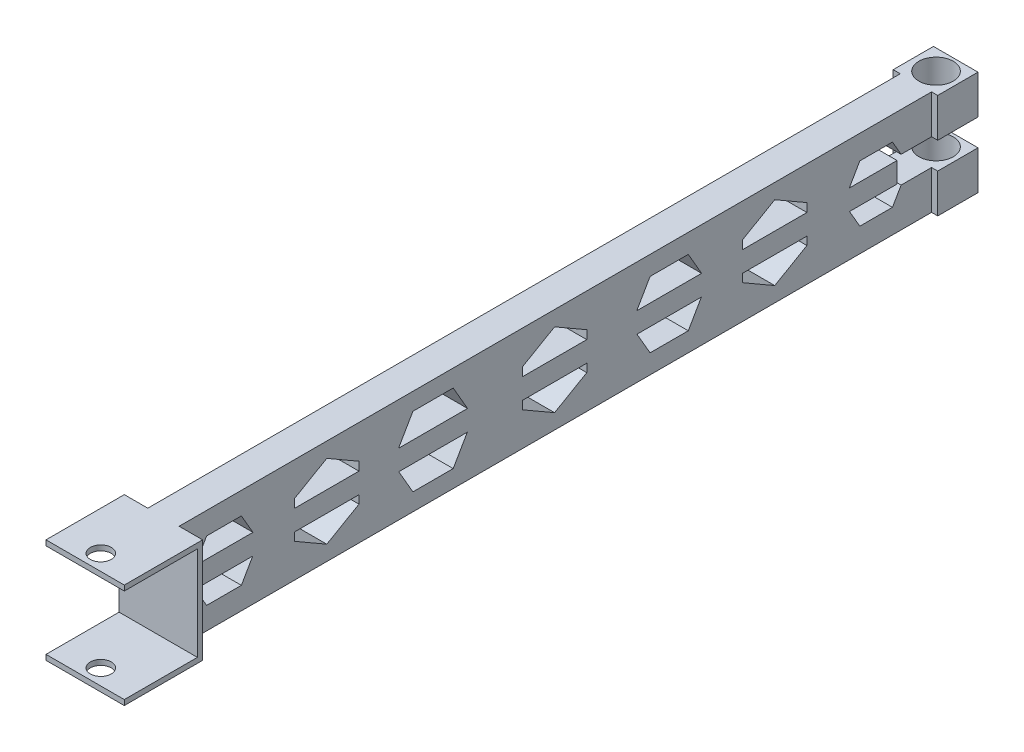
SolidWorks part; units mm, degrees
ref_plane "前视基准面" through (0, 0, 0) normal (0, 0, 1) x (1, 0, 0)
ref_plane "上视基准面" through (0, 0, 0) normal (0, 1, 0) x (1, 0, 0)
ref_plane "右视基准面" through (0, 0, 0) normal (1, 0, 0) x (0, 0, -1)
sketch "草图1" plane through (0, 0, 0) normal (0, 0, 1) x (1, 0, 0)
  line L1 (-3, -10) -> (3, -10)
  line L2 (-3, -10) -> (-3, 10)
  line L3 (-3, 10) -> (3, 10)
  line L4 (3, -10) -> (3, 10)
  line L5 (-3, -10) -> (3, 10) construction
  line L6 (-3, 10) -> (3, -10) construction
  point P0 (0, 0)
extrude "凸台-拉伸1" add sketch "草图1" along normal blind 165
sketch "草图2" plane through (3, 0, 0) normal (1, 0, 0) x (0, 0, -1)
  line L0 (0, 0) -> (-5, 0)
hole_wizard "G1/16 螺纹孔1" positions "草图3" profile "草图4" tap size "G1/16" standard "GB"
sketch "草图3" plane through (3, 0, 0) normal (1, 0, 0) x (0, 0, -1)
  point P0 (-5, 0)
sketch "草图4" plane through (3, 0, 5) normal (0, 1, 0) x (0, 0, -1)
  line L0 (0, 0) -> (0, 51.9828)
  line L1 (0, 51.9828) -> (3.3, 50)
  line L2 (3.3, 50) -> (3.3, 0.5865)
  line L3 (3.3, 0.5865) -> (3.8865, 0)
  line L5 (3.8865, 0) -> (0, 0)
  line L6 (-3.3, 0.5865) -> (-3.8865, 0) construction
  line L10 (0, 51.9828) -> (-3.3, 50) construction
  line L11 (0, -6.35) -> (0, 107.95) construction
  dimension "螺纹孔钻头直径" = 6.6
  dimension "螺纹孔钻头深度" = 50
  dimension "近端锥形沉头孔直径" = 7.773
  dimension "近端锥形沉头孔角度" = 90
  dimension "导头角度" = 118
cosmetic thread "孔螺蚊线1" parameters "D1"=15.45, "D2"=7.723
sketch "草图5" plane through (3, 0, 0) normal (1, 0, 0) x (0, 0, -1)
  line L1 (-168, -10) -> (-153, -10)
  line L2 (-168, -10) -> (-168, 10)
  line L3 (-168, 10) -> (-153, 10)
  line L4 (-153, -10) -> (-153, 10)
  line L5 (-168, -10) -> (-153, 10) construction
  line L6 (-168, 10) -> (-153, -10) construction
  point P0 (-160.5, 0)
extrude "凸台-拉伸2" add sketch "草图5" along normal blind 10 and the other way blind 15
sketch "草图6" plane through (0, -10, 0) normal (0, -1, 0) x (1, 0, 0)
  line L0 (-12, 168) -> (13, 168) construction
  line L1 (-7.5, 168) -> (7.5, 168)
  line L2 (-7.5, 168) -> (-7.5, 153)
  line L3 (-7.5, 153) -> (7.5, 153)
  line L4 (7.5, 168) -> (7.5, 153)
  line L5 (3, 153) -> (13, 153) construction
  line L6 (-7.5, 153) -> (-12, 153)
  line L7 (-12, 153) -> (-12, 168)
  line L8 (-12, 168) -> (-12, 153) construction
  line L9 (-12, 168) -> (-7.5, 168)
  line L10 (7.5, 168) -> (13, 168)
  line L11 (13, 168) -> (13, 153) construction
  line L12 (13, 168) -> (13, 153)
  line L13 (13, 153) -> (7.5, 153)
  line M4 (3, 153) -> (13, 153)
  line M5 (13, 153) -> (13, 168)
  line M6 (13, 168) -> (-12, 168)
  line M7 (-12, 168) -> (-12, 153)
  line M8 (-12, 153) -> (-3, 153)
extrude "切除-拉伸1" cut sketch "草图6" against normal blind 32 contours L4 M6 M4 M5 | L2 M6 M7 M8 region at (-9.75, -10, 160.5) region at (10.25, -10, 160.5)
sketch "草图7" plane through (0, 0, 168) normal (0, 0, 1) x (1, 0, 0)
  line L1 (-7.5, 10) -> (-7.5, -10) construction
  line L2 (7.5, 9) -> (-7.5, 9)
  line L3 (7.5, 9) -> (7.5, -9)
  line L4 (7.5, -9) -> (-7.5, -9)
  line L5 (-7.5, 9) -> (-7.5, -9)
  line L6 (7.5, 9) -> (-7.5, -9) construction
  line L7 (7.5, -9) -> (-7.5, 9) construction
  point P2 (0, 0)
extrude "切除-拉伸2" cut sketch "草图7" against normal blind 14
sketch "草图8" plane through (0, 10, 0) normal (0, 1, 0) x (1, 0, 0)
  line L0 (3, -1.1135) -> (3, -8.8865)
  line L1 (3, -8.8865) -> (3, -5)
  line L2 (3, -5) -> (0, -5)
  line L3 (0, -5) -> (0, -165)
  circle A0 centre (0, -165) radius 2
extrude "切除-拉伸3" cut sketch "草图8" against normal blind 39 contours A0
sketch "草图9" plane through (-3, 0, 0) normal (-1, 0, 0) x (0, 0, 1)
  line L0 (154, 9) -> (154, -9) construction
  line L1 (151.0541, 0) -> (147.728, 5.761)
  line L2 (147.728, 5.761) -> (141.0758, 5.761)
  line L3 (141.0758, 5.761) -> (137.7497, 0)
  line L4 (137.7497, 0) -> (141.0758, -5.761)
  line L5 (141.0758, -5.761) -> (147.728, -5.761)
  line L6 (147.728, -5.761) -> (151.0541, 0)
  line L7 (124.7114, -7.1178) -> (130.8757, -3.5589)
  line L8 (130.8757, -3.5589) -> (130.8757, 3.5589)
  line L9 (130.8757, 3.5589) -> (124.7114, 7.1178)
  line L10 (124.7114, 7.1178) -> (118.5472, 3.5589)
  line L11 (118.5472, 3.5589) -> (118.5472, -3.5589)
  line L12 (118.5472, -3.5589) -> (124.7114, -7.1178)
  line L13 (112.0723, 0) -> (108.214, 6.6827)
  line L14 (108.214, 6.6827) -> (100.4974, 6.6827)
  line L15 (100.4974, 6.6827) -> (96.6392, 0)
  line L16 (96.6392, 0) -> (100.4974, -6.6827)
  line L17 (100.4974, -6.6827) -> (108.214, -6.6827)
  line L18 (108.214, -6.6827) -> (112.0723, 0)
  line L19 (81.073, 7.1178) -> (74.9088, 3.5589)
  line L20 (74.9088, 3.5589) -> (74.9088, -3.5589)
  line L21 (74.9088, -3.5589) -> (81.073, -7.1178)
  line L22 (81.073, -7.1178) -> (87.2373, -3.5589)
  line L23 (87.2373, -3.5589) -> (87.2373, 3.5589)
  line L24 (87.2373, 3.5589) -> (81.073, 7.1178)
  line L25 (66.4382, 0) -> (62.7795, 6.3371)
  line L26 (62.7795, 6.3371) -> (55.4621, 6.3371)
  line L27 (55.4621, 6.3371) -> (51.8034, 0)
  line L28 (51.8034, 0) -> (55.4621, -6.3371)
  line L29 (55.4621, -6.3371) -> (62.7795, -6.3371)
  line L30 (62.7795, -6.3371) -> (66.4382, 0)
  line L31 (38.8981, 7.1178) -> (32.7339, 3.5589)
  line L32 (32.7339, 3.5589) -> (32.7339, -3.5589)
  line L33 (32.7339, -3.5589) -> (38.8981, -7.1178)
  line L34 (38.8981, -7.1178) -> (45.0624, -3.5589)
  line L35 (45.0624, -3.5589) -> (45.0624, 3.5589)
  line L36 (45.0624, 3.5589) -> (38.8981, 7.1178)
  line L37 (25.7268, 0) -> (22.6003, 5.4153)
  line L38 (22.6003, 5.4153) -> (16.3472, 5.4153)
  line L39 (16.3472, 5.4153) -> (13.2207, 0)
  line L40 (13.2207, 0) -> (16.3472, -5.4153)
  line L41 (16.3472, -5.4153) -> (22.6003, -5.4153)
  line L42 (22.6003, -5.4153) -> (25.7268, 0)
  line L43 (154, -1.9955) -> (11.8642, -1.9955)
  line L44 (154, -1.9955) -> (154, 1.9187)
  line L45 (154, 1.9187) -> (11.8642, 1.9187)
  line L46 (11.8642, -1.9955) -> (11.8642, 1.9187)
  circle A0 centre (144.4019, 0) radius 5.761 construction
  circle A1 centre (124.7114, 0) radius 6.1642 construction
  circle A2 centre (104.3557, 0) radius 6.6827 construction
  circle A3 centre (81.073, 0) radius 6.1642 construction
  circle A4 centre (59.1208, 0) radius 6.3371 construction
  circle A5 centre (38.8981, 0) radius 6.1642 construction
  circle A6 centre (19.4737, 0) radius 5.4153 construction
extrude "切除-拉伸4" cut sketch "草图9" against normal blind 70 contours L45 L37 L38 L39 | L42 L43 L40 L41 | L45 L35 L36 L31 L32 | L35 L43 L32 L33 L34 | L45 L25 L26 L27 | L30 L43 L28 L29 | L23 L43 L20 L21 L22 | L45 L23 L24 L19 L20 | L45 L13 L14 L15 | L18 L43 L16 L17 | L45 L8 L9 L10 L11 | L8 L43 L11 L12 L7 | L45 L1 L2 L3 | L6 L43 L4 L5 region at (-3, 3.6797, 144.4019) region at (-3, -3.7237, 144.4019) region at (-3, 3.7829, 124.7114) region at (-3, -3.8248, 124.7114) region at (-3, 4.0921, 104.3557) region at (-3, -4.1363, 104.3557) region at (-3, 3.7829, 81.073) region at (-3, -3.8248, 81.073) region at (-3, 3.9375, 59.1208) region at (-3, -3.9817, 59.1208) region at (-3, 3.7829, 38.8981) region at (-3, -3.8248, 38.8981) region at (-3, 3.5248, 19.4737) region at (-3, -3.5686, 19.4737)
sketch "草图10" plane through (3, 0, 0) normal (1, 0, 0) x (0, 0, -1)
  line L0 (-5, 0) -> (-5, -10)
  line L1 (-153, -10) -> (0, -10) construction
sketch "草图11" plane through (0, -10, 0) normal (0, -1, 0) x (-1, 0, 0)
  line L0 (4.3561, -1.1416) -> (3, 0)
  line L1 (4.3561, -8.8602) -> (-4.1787, -8.8602)
  line L2 (4.3561, -8.8602) -> (4.3561, -1.1416)
  line L3 (4.3561, -1.1416) -> (-4.1787, -1.1416)
  line L4 (-4.1787, -8.8602) -> (-4.1787, -1.1416)
  line L5 (3, 0) -> (-3, 0)
  line L6 (3, 0) -> (-3, 0) construction
  line L7 (-3, 0) -> (-4.1787, -1.1416)
  circle A0 centre (0, -5) radius 3.3
  line M10 (3, -153) -> (3, 0)
  line M11 (3, 0) -> (-3, 0)
  line M12 (-3, 0) -> (-3, -153)
extrude "凸台-拉伸3" add sketch "草图11" against normal blind 20 contours A0 L3 L4 L1 M12 | A0 L1 L2 L3 M10 | A0 L3 M10 M12 | A0 L1 M12 M10 region at (-3.7093, -10, 5.0009) region at (-2.9351, -10, 2.3834) region at (0, -10, 8.7952) region at (3.6198, -10, 5.0009)
extrude "切除-拉伸5" cut sketch "草图11<5>" against normal blind 20 contours L3 M10 M11 M12 | A0 M12 M10 region at (0, -10, 0.5708) region at (0, -10, 5)
sketch "草图11<5>" plane through (0, -10, 0) normal (0, -1, 0) x (-1, 0, 0) same geometry as "草图11"
sketch "草图13" plane through (4.1787, 0, 0) normal (1, 0, 0) x (0, 0, -1)
  line L0 (-1.1416, 10) -> (-1.1416, -10) construction
  line L1 (-8.8584, -2.55) -> (-1.1416, -2.55)
  line L3 (-8.8584, 2.55) -> (-1.1416, 2.55)
  line L4 (-1.1416, -2.55) -> (-1.1416, 2.55)
  line L5 (-8.8584, -2.55) -> (-1.1416, 2.55) construction
  line L6 (-8.8584, 2.55) -> (-1.1416, -2.55) construction
  line L7 (-8.8584, -2.55) -> (-15.4731, -2.55)
  line L8 (-15.4731, -2.55) -> (-15.4731, 2.55)
  line L9 (-15.4731, 2.55) -> (-8.8584, 2.55)
  point P0 (-5, 0)
  line M2 (-1.1416, -10) -> (-1.1416, 10)
  line M4 (-8.8602, 10) -> (-8.8602, -10)
extrude "切除-拉伸6" cut sketch "草图13" against normal blind 20 contours L9 L8 L7 M4 | L3 L1 M2 region at (4.1787, 0, 5.0009) region at (4.1787, 0, 12.1666)
